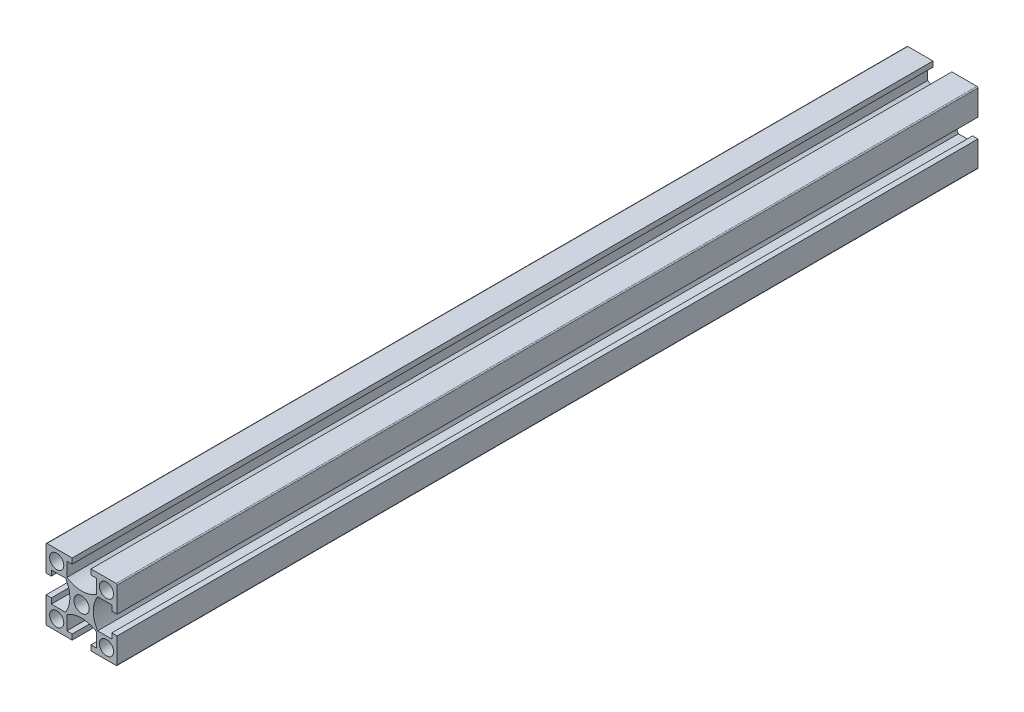
SolidWorks part; units mm, degrees
material "3.0255 (EN-AW 1350A)"
ref_plane "정면" through (0, 0, 0) normal (0, 0, 1) x (1, 0, 0)
ref_plane "윗면" through (0, 0, 0) normal (0, 1, 0) x (1, 0, 0)
ref_plane "우측면" through (0, 0, 0) normal (1, 0, 0) x (0, 0, -1)
sketch "스케치1" plane through (0, 0, 0) normal (0, 0, 1) x (1, 0, 0)
  line L0 (0, 32.0265) -> (0, -31.6588) construction
  line L1 (-10, 10) -> (-10, -10)
  line L2 (-10, 10) -> (10, 10)
  line L3 (-10, 2.65) -> (-8.5, 2.65)
  line L4 (13.6618, 0) -> (-11.6993, 0) construction
  line L5 (-8.5, 2.65) -> (-8.5, 4.15)
  line L6 (-8.5, 4.15) -> (-4.5032, 4.15)
  line L7 (-10, -2.65) -> (-8.5, -2.65)
  line L8 (-8.5, -2.65) -> (-8.5, -4.15)
  line L9 (-8.5, -4.15) -> (-4.5032, -4.15)
  line L10 (-10, -10) -> (10, -10)
  line L11 (10, 10) -> (10, -10)
  circle A0 centre (-7, 7) radius 2
  circle A1 centre (-7, -7) radius 2
  arc A2 (-4.5032, 4.15) -> (-4.5032, -4.15) centre (-11.0587, 0) cw
  circle A3 centre (0, 0) radius 2.15
  circle A4 centre (7, 7) radius 2
  circle A5 centre (7, -7) radius 2
  point P21 (-10, 0)
  point P23 (-3.3, 0)
  point P31 (0, -10)
  point P32 (0, 10)
  dimension "D3" = 4
  dimension "D9" = 6.7
  dimension "D10" = 4.3
  dimension "D11" = 7.7587
  dimension "D1" = 20
  dimension "D2" = 20
  dimension "D4" = 14
  dimension "D5" = 14
  dimension "D6" = 5.3
  dimension "D7" = 8.3
  dimension "D8" = 1.5
extrude "보스-돌출1" add sketch "스케치1" along normal blind 242 contours A0 | A4 | A3 | A5 | A1 | A2 L6 L5 L3 L1 L7 L8 L9 | L2 L11 L10 L1 region at (-6.6069, 0, 0) region at (-7, 7, 0) region at (-7, -7, 0) region at (0, 0, 0) region at (7, 7, 0) region at (7, -7, 0)
extrude "컷-돌출1" cut sketch "스케치1<3>" along normal up to next contours A2 L6 L5 L3 L1 L7 L8 L9 region at (-6.6069, 0, 0)
sketch "스케치1<3>" plane through (0, 0, 0) normal (0, 0, 1) x (1, 0, 0) same geometry as "스케치1"
pattern_circular "원형 패턴1" count 4 over 360 about axis through (0, 0, 242) along (0, 0, -1) of "컷-돌출1" reverse direction yes
fillet "필렛1" radius 0.3 4 edges at (10, -10, 121) (-10, -10, 121) (-10, 10, 121) (10, 10, 121)
sketch "스케치2" plane through (0, 10, 0) normal (0, 1, 0) x (1, 0, 0)
  line L0 (-9.7, -20) -> (9.7, -20) construction
  line L1 (-9.7, 0) -> (-9.7, -242) construction
  line L2 (9.7, -242) -> (9.7, 0) construction
  line L4 (2.65, 0) -> (9.7, 0) construction
  line L5 (-4.15, -242) -> (4.15, -242) construction
  circle A0 centre (0, -215) radius 2.5
  circle A1 centre (0, -10) radius 2.5
  circle A2 centre (0, -186) radius 2.5
  dimension "D1" = 27
  dimension "D3" = 56
  dimension "D2" = 10
extrude "컷-돌출2" cut sketch "스케치2" against normal through all
ref_plane "평면1" through (-9.7, 10, 0) normal (0, 0, 1) x (1, 0, 0)
